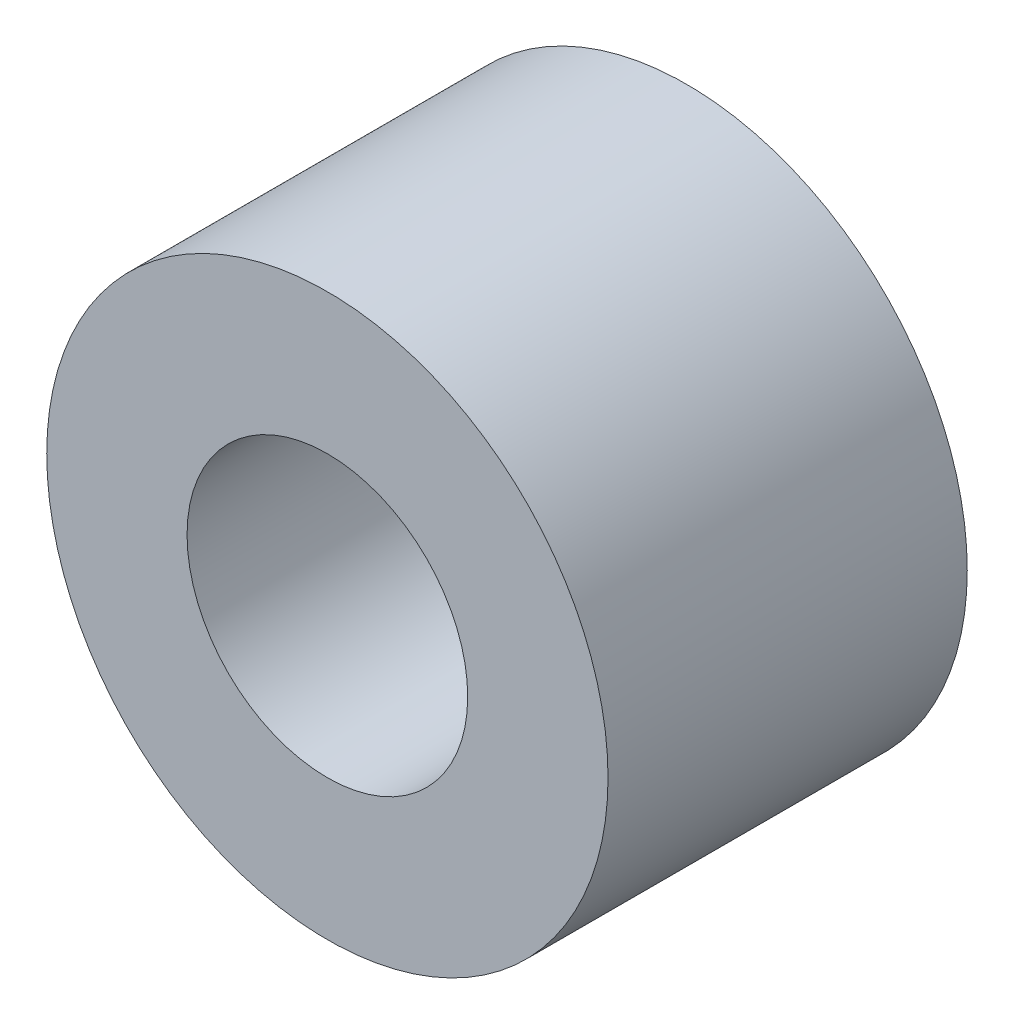
SolidWorks part; units mm, degrees
ref_plane "Front Plane" through (0, 0, 0) normal (0, 0, 1) x (1, 0, 0)
ref_plane "Top Plane" through (0, 0, 0) normal (0, 1, 0) x (1, 0, 0)
ref_plane "Right Plane" through (0, 0, 0) normal (1, 0, 0) x (0, 0, -1)
sketch "Sketch1" plane through (0, 0, 0) normal (0, 0, 1) x (1, 0, 0)
  circle A0 centre (0, 0) radius 6.35
  circle A1 centre (0, 0) radius 3.175
  dimension "D1" = 12.7
  dimension "D2" = 6.35
extrude "Boss-Extrude1" add sketch "Sketch1" along normal blind 8.128
ref_axis "Axis1" through (0, 0, 8.128) along (0, 0, -1)
